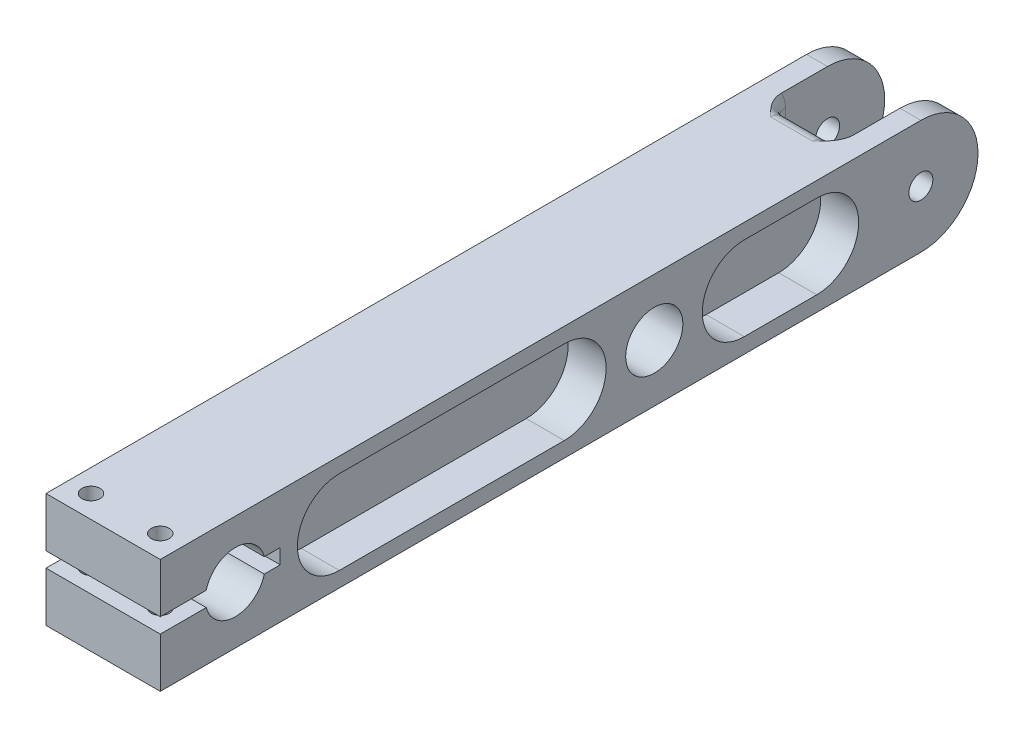
SolidWorks part; units mm, degrees
material "6061-T6 (SS)"
ref_plane "Front Plane" through (0, 0, 0) normal (0, 0, 1) x (1, 0, 0)
ref_plane "Top Plane" through (0, 0, 0) normal (0, 1, 0) x (1, 0, 0)
ref_plane "Right Plane" through (0, 0, 0) normal (1, 0, 0) x (0, 0, -1)
sketch "Sketch1" plane through (0, 0, 0) normal (1, 0, 0) x (0, 0, -1)
  line L0 (0, 0) -> (247.65, 0)
  line L1 (0, 0) -> (247.65, 0)
  line L2 (0, 0) -> (0, 38.1)
  line L3 (247.65, 0) -> (247.65, 38.1)
  line L4 (0, 38.1) -> (247.65, 38.1)
  line L5 (0, 0) -> (0, 38.1)
  line L6 (0, 0) -> (-25, 0)
  line L7 (0, 38.1) -> (-25, 38.1)
  line L8 (-25, 0) -> (-25, 38.1)
  line L9 (0, 16.55) -> (-25, 16.55)
  line L10 (0, 16.55) -> (0, 21.55)
  line L11 (-25, 16.55) -> (-25, 21.55)
  line L12 (0, 21.55) -> (-25, 21.55)
  line L13 (0, 16.55) -> (0, 21.55)
  line L14 (0, 16.55) -> (15, 16.55)
  line L15 (0, 21.55) -> (15, 21.55)
  line L16 (15, 16.55) -> (15, 21.55)
  circle A0 centre (0, 0) radius 247.65
  circle A2 centre (139.7, 19.05) radius 9.525
  circle A3 centre (228.6, 19.05) radius 4
  circle A4 centre (0, 19.05) radius 10
  dimension "D1" = 495.3
  dimension "D4" = 19.05
  dimension "D5" = 8
  dimension "D10" = 20
  dimension "D2" = 38.1
  dimension "D3" = 247.65
  dimension "D6" = 19.05
  dimension "D7" = 19.05
  dimension "D8" = 19.05
  dimension "D9" = 25
  dimension "D11" = 139.7
  dimension "D12" = 2.5
  dimension "D13" = 5
  dimension "D14" = 15
extrude "Boss-Extrude1" add sketch "Sketch1" along normal blind 38.1 contours L0 A0 L4 L2 | A0 L3 L4 | A4 L9 L8 L6 L2 | A4 L5 L7 L8 L12 region at (0, 19.0099, -124.6406) region at (0, 7.505, 13.7824) region at (0, 28.5864, -246.7664) region at (0, 30.595, 13.7824)
fillet "Fillet1" radius 19.05 2 edges at (19.05, 0, -247.65) (19.05, 38.1, -247.65)
sketch "Sketch2" plane through (0, 38.1, 0) normal (0, 1, 0) x (1, 0, 0)
  line L0 (6.985, 209.55) -> (6.985, 247.65)
  line L1 (6.985, 209.55) -> (31.115, 209.55)
  line L2 (6.985, 247.65) -> (31.115, 247.65)
  line L3 (31.115, 209.55) -> (31.115, 247.65)
  line L4 (6.985, 209.55) -> (31.115, 247.65) construction
  line L5 (6.985, 247.65) -> (31.115, 209.55) construction
  line L6 (38.1, 228.6) -> (0, 228.6) construction
  point P1 (19.05, 228.6)
  dimension "D1" = 24.13
extrude "Cut-Extrude1" cut sketch "Sketch2" against normal through all
sketch "Sketch3" plane through (38.1, 0, 0) normal (1, 0, 0) x (0, 0, -1)
  line L0 (34.7, 19.05) -> (109.7, 19.05) construction
  line L1 (34.7, 33.02) -> (109.7, 33.02)
  line L2 (-25, 0) -> (228.6, 0)
  line L3 (228.6, 38.1) -> (-25, 38.1)
  line L4 (-25, 0) -> (228.6, 0)
  line L5 (228.6, 38.1) -> (-25, 38.1)
  line L6 (34.7, 5.08) -> (109.7, 5.08)
  line L7 (169.7, 19.05) -> (193.9, 19.05) construction
  line L8 (169.7, 33.02) -> (193.9, 33.02)
  line L9 (169.7, 5.08) -> (193.9, 5.08)
  line L14 (-25, 38.1) -> (-25, 21.55)
  line L16 (-25, 38.1) -> (-25, 21.55)
  line L23 (-25, 21.55) -> (-9.6825, 21.55)
  line L24 (-25, 21.55) -> (-9.6825, 21.55)
  line L25 (9.6825, 21.55) -> (15, 21.55)
  line L26 (9.6825, 21.55) -> (15, 21.55)
  line L27 (15, 21.55) -> (15, 16.55)
  line L28 (15, 21.55) -> (15, 16.55)
  line L29 (15, 16.55) -> (9.6825, 16.55)
  line L30 (15, 16.55) -> (9.6825, 16.55)
  line L31 (-9.6825, 16.55) -> (-25, 16.55)
  line L32 (-9.6825, 16.55) -> (-25, 16.55)
  line L33 (-25, 16.55) -> (-25, 0)
  line L34 (-25, 16.55) -> (-25, 0)
  arc A0 (34.7, 33.02) -> (34.7, 5.08) centre (34.7, 19.05) ccw
  arc A1 (109.7, 5.08) -> (109.7, 33.02) centre (109.7, 19.05) ccw
  circle A2 centre (139.7, 19.05) radius 9.525 construction
  arc A3 (228.6, 0) -> (247.65, 19.05) centre (228.6, 19.05) ccw
  arc A4 (247.65, 19.05) -> (228.6, 38.1) centre (228.6, 19.05) ccw
  arc A5 (9.6825, 21.55) -> (-9.6825, 21.55) centre (0, 19.05) ccw
  arc A6 (228.6, 0) -> (247.65, 19.05) centre (228.6, 19.05) ccw
  arc A7 (247.65, 19.05) -> (228.6, 38.1) centre (228.6, 19.05) ccw
  circle A9 centre (0, 19.05) radius 31.4309
  arc A10 (169.7, 33.02) -> (169.7, 5.08) centre (169.7, 19.05) ccw
  arc A11 (193.9, 5.08) -> (193.9, 33.02) centre (193.9, 19.05) ccw
  circle A12 centre (228.6, 19.05) radius 19.05
  arc A18 (9.6825, 21.55) -> (-9.6825, 21.55) centre (0, 19.05) ccw
  arc A19 (-9.6825, 16.55) -> (9.6825, 16.55) centre (0, 19.05) ccw
  arc A20 (-9.6825, 16.55) -> (9.6825, 16.55) centre (0, 19.05) ccw
  point P10 (72.2, 19.05)
  point P20 (181.8, 19.05)
  dimension "D2" = 75
  dimension "D3" = 13.97
  dimension "D5" = 30
  dimension "D6" = 34.7
  dimension "D4" = 30
  dimension "D1" = 0
extrude "Cut-Extrude2" cut sketch "Sketch3" against normal blind 12.7 contours L6 A1 L1 A0 | L9 A11 L8 A10 | A0 A9 region at (38.1, 19.05, -75.6731) region at (38.1, 19.05, -26.4957) region at (38.1, 19.05, -181.8)
ref_plane "Plane1" through (19.05, 0, 0) normal (1, 0, 0) x (0, 0, -1)
mirror "Mirror1" about plane through (19.05, 0, 0) normal (1, 0, 0) of "Cut-Extrude2"
sketch "Sketch4" plane through (0, 38.1, 0) normal (0, 1, 0) x (1, 0, 0)
  line L0 (38.1, -25) -> (0, -25)
  line L1 (38.1, -25) -> (38.1, 0)
  line L2 (0, -25) -> (0, 0)
  line L3 (38.1, 0) -> (0, 0)
  line L4 (38.1, 0) -> (38.1, -10)
  line L5 (38.1, 0) -> (0, 0)
  line L6 (38.1, -10) -> (0, -10)
  line L7 (0, 0) -> (0, -10)
  line L8 (6.985, 209.55) -> (6.985, 228.6)
  line L9 (6.985, 228.6) -> (0, 228.6)
  line L10 (0, 228.6) -> (0, -25)
  line L11 (0, -25) -> (38.1, -25)
  line L12 (38.1, -25) -> (38.1, 228.6)
  line L13 (38.1, 228.6) -> (31.115, 228.6)
  line L14 (31.115, 228.6) -> (31.115, 209.55)
  line L15 (31.115, 209.55) -> (6.985, 209.55)
  line L16 (6.985, 209.55) -> (6.985, 228.6)
  line L17 (6.985, 228.6) -> (0, 228.6)
  line L18 (0, 228.6) -> (0, -25)
  line L19 (0, -25) -> (38.1, -25)
  line L20 (38.1, -25) -> (38.1, 228.6)
  line L21 (38.1, 228.6) -> (31.115, 228.6)
  line L22 (31.115, 228.6) -> (31.115, 209.55)
  line L23 (31.115, 209.55) -> (6.985, 209.55)
  circle A0 centre (7.5, -17.5) radius 3
  circle A1 centre (30.6, -17.5) radius 3
  point P17 (0, 0)
  dimension "D9" = 6
  dimension "D10" = 6
  dimension "D2" = 25
  dimension "D3" = 10
  dimension "D4" = 38.1
  dimension "D5" = 7.5
  dimension "D6" = 7.5
  dimension "D7" = 7.5
  dimension "D8" = 7.5
  dimension "D1" = 0
extrude "Cut-Extrude3" cut sketch "Sketch4" against normal through all contours A0 | A1 region at (7.5, 38.1, 17.5)
fillet "Fillet4" radius 5 2 edges at (19.05, 0, -209.55) (19.05, 38.1, -209.55)
fillet "Fillet5" radius 5 6 edges at (6.985, 1.4645, -208.0855) (6.985, 36.6355, -208.0855) (31.115, 1.4645, -208.0855) (31.115, 36.6355, -208.0855) (6.985, 19.05, -209.55) (31.115, 19.05, -209.55)
